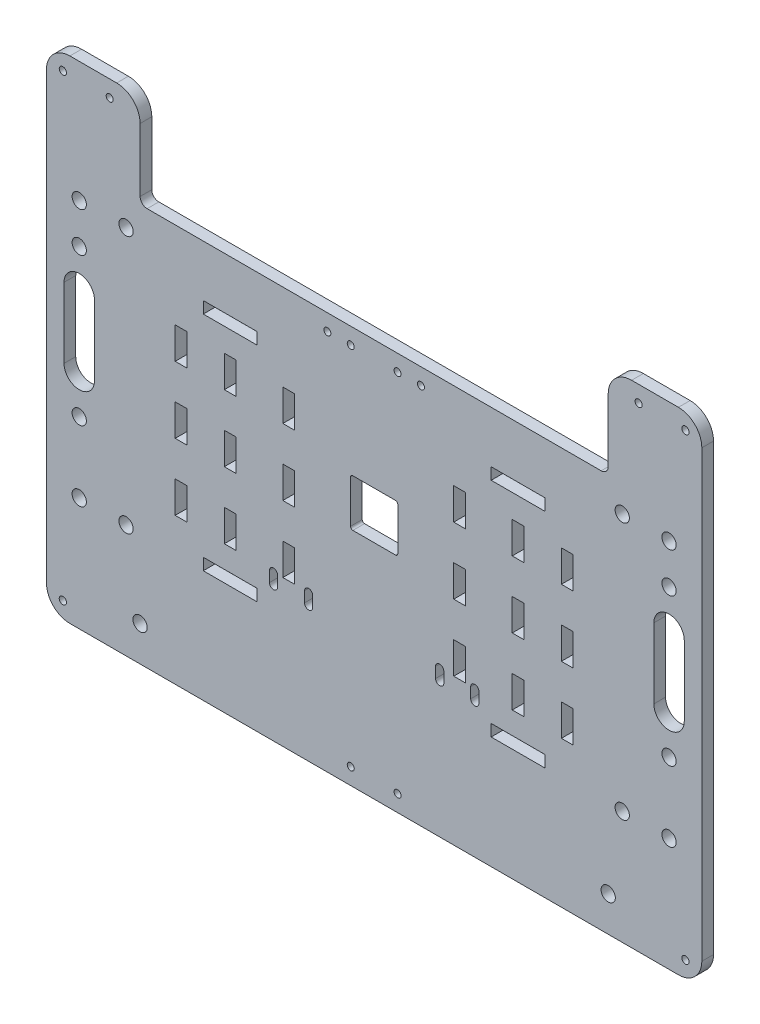
SolidWorks part; units mm, degrees
material "Acrylique (impact moyen-haut)"
ref_plane "Plan de face" through (0, 0, 0) normal (0, 0, 1) x (1, 0, 0)
ref_plane "Plan de dessus" through (0, 0, 0) normal (0, 1, 0) x (1, 0, 0)
ref_plane "Plan de droite" through (0, 0, 0) normal (1, 0, 0) x (0, 0, -1)
sketch "Esquisse1" plane through (0, 0, 0) normal (0, 0, 1) x (1, 0, 0)
  line L1 (130, -105) -> (-130, -105)
  line L2 (140, -95) -> (140, 105)
  line L3 (140, 105) -> (-140, 105)
  line L4 (-140, -95) -> (-140, 105)
  line L5 (140, -105) -> (-140, 105) construction
  line L6 (140, 105) -> (-140, -105) construction
  arc A0 (130, -105) -> (140, -95) centre (130, -95) ccw
  arc A1 (-130, -105) -> (-140, -95) centre (-130, -95) cw
  point P0 (0, 0)
  dimension "D3" = 10
  dimension "D1" = 210
  dimension "D2" = 280
extrude "Boss.-Extru.1" add sketch "Esquisse1" along normal blind 5
sketch "Esquisse2" plane through (0, 0, 5) normal (0, 0, 1) x (1, 0, 0)
  line L0 (-39.01, -0.5) -> (-39.01, -14)
  line L1 (-39.01, 28) -> (-34, 28)
  line L2 (-39.01, 28) -> (-39.01, 14.5)
  line L3 (-39.01, 14.5) -> (-34, 14.5)
  line L4 (-34, 28) -> (-34, 14.5)
  line L5 (-39.01, -0.5) -> (-34, -0.5)
  line L6 (-34, -0.5) -> (-34, -14)
  line L7 (-39.01, -14) -> (-34, -14)
  line L8 (-39.01, -29) -> (-39.01, -42.5)
  line L9 (-39.01, -29) -> (-34, -29)
  line L10 (-34, -29) -> (-34, -42.5)
  line L11 (-39.01, -42.5) -> (-34, -42.5)
  line L12 (-64.01, -0.5) -> (-64.01, -14)
  line L13 (-64.01, 28) -> (-59, 28)
  line L14 (-64.01, 28) -> (-64.01, 14.5)
  line L15 (-64.01, 14.5) -> (-59, 14.5)
  line L16 (-59, 28) -> (-59, 14.5)
  line L17 (-64.01, -0.5) -> (-59, -0.5)
  line L18 (-59, -0.5) -> (-59, -14)
  line L19 (-64.01, -14) -> (-59, -14)
  line L20 (-64.01, -29) -> (-64.01, -42.5)
  line L21 (-64.01, -29) -> (-59, -29)
  line L22 (-59, -29) -> (-59, -42.5)
  line L23 (-64.01, -42.5) -> (-59, -42.5)
  line L24 (-85.01, 28) -> (-85.01, 14.5)
  line L25 (-85.01, 28) -> (-80, 28)
  line L26 (-85.01, -0.5) -> (-85.01, -14)
  line L27 (-85.01, 14.5) -> (-80, 14.5)
  line L28 (-80, 28) -> (-80, 14.5)
  line L29 (-85.01, -0.5) -> (-80, -0.5)
  line L30 (-80, -0.5) -> (-80, -14)
  line L31 (-85.01, -14) -> (-80, -14)
  line L32 (-85.01, -29) -> (-85.01, -42.5)
  line L33 (-85.01, -29) -> (-80, -29)
  line L34 (-80, -29) -> (-80, -42.5)
  line L35 (-85.01, -42.5) -> (-80, -42.5)
  line L36 (85.01, 14.5) -> (80, 14.5)
  line L37 (50, -51.99) -> (50, -57)
  line L38 (73.01, -57) -> (50, -57)
  line L39 (73.01, -51.99) -> (73.01, -57)
  line L40 (73.01, -51.99) -> (50, -51.99)
  line L41 (50, 43) -> (50, 37.99)
  line L42 (73.01, 37.99) -> (50, 37.99)
  line L43 (73.01, 43) -> (73.01, 37.99)
  line L44 (73.01, 43) -> (50, 43)
  line L45 (85.01, -42.5) -> (80, -42.5)
  line L46 (80, -29) -> (80, -42.5)
  line L47 (85.01, -29) -> (80, -29)
  line L48 (85.01, -29) -> (85.01, -42.5)
  line L49 (85.01, -14) -> (80, -14)
  line L50 (80, -0.5) -> (80, -14)
  line L51 (85.01, -0.5) -> (80, -0.5)
  line L52 (80, 28) -> (80, 14.5)
  line L53 (85.01, 14.5) -> (80, 14.5)
  line L54 (85.01, -0.5) -> (85.01, -14)
  line L55 (85.01, 28) -> (80, 28)
  line L56 (85.01, 28) -> (85.01, 14.5)
  line L57 (64.01, -42.5) -> (59, -42.5)
  line L58 (59, -29) -> (59, -42.5)
  line L59 (64.01, -29) -> (59, -29)
  line L60 (64.01, -29) -> (64.01, -42.5)
  line L61 (64.01, -14) -> (59, -14)
  line L62 (59, -0.5) -> (59, -14)
  line L63 (64.01, -0.5) -> (59, -0.5)
  line L64 (59, 28) -> (59, 14.5)
  line L65 (64.01, 14.5) -> (59, 14.5)
  line L66 (64.01, 28) -> (64.01, 14.5)
  line L67 (64.01, 28) -> (59, 28)
  line L68 (64.01, -0.5) -> (64.01, -14)
  line L69 (39.01, -42.5) -> (34, -42.5)
  line L70 (34, -29) -> (34, -42.5)
  line L71 (39.01, -29) -> (34, -29)
  line L72 (39.01, -29) -> (39.01, -42.5)
  line L73 (39.01, -14) -> (34, -14)
  line L74 (0, 0) -> (0, 77.3847) construction
  line L75 (-73.01, 43) -> (-50, 43)
  line L76 (-73.01, 43) -> (-73.01, 37.99)
  line L77 (-73.01, 37.99) -> (-50, 37.99)
  line L78 (-50, 43) -> (-50, 37.99)
  line L79 (-73.01, -51.99) -> (-50, -51.99)
  line L80 (-73.01, -51.99) -> (-73.01, -57)
  line L81 (-73.01, -57) -> (-50, -57)
  line L82 (-50, -51.99) -> (-50, -57)
  line L83 (34, -0.5) -> (34, -14)
  line L84 (39.01, -0.5) -> (34, -0.5)
  line L85 (34, 28) -> (34, 14.5)
  line L86 (39.01, 14.5) -> (34, 14.5)
  line L87 (39.01, 28) -> (39.01, 14.5)
  line L88 (39.01, 28) -> (34, 28)
  line L89 (39.01, -0.5) -> (39.01, -14)
  line L90 (-140, 105) -> (-140, -95) construction
  line L91 (-130, -105) -> (130, -105) construction
  line L102 (-85.01, 14.5) -> (-80, 14.5)
  line L104 (-85.01, -0.5) -> (-80, -0.5)
  line L189 (-85.01, -0.5) -> (-85.01, -14) [skipped]
  line L190 (-85.01, 28) -> (-85.01, 14.5) [skipped]
  point P90 (81.49, 5)
  point P148 (-81.49, 5)
  dimension "D2" = 15
  dimension "D3" = 23.01
  dimension "D4" = 2
  dimension "D6" = 100
  dimension "D7" = 5.01
  dimension "D8" = 13.5
  dimension "D9" = 72
  dimension "D10" = 3
  dimension "D11" = 2
  dimension "D12" = 25
  dimension "D13" = 46
  dimension "D14" = 2
  dimension "D15" = 106
  dimension "D16" = 62.5
  dimension "D19" = 16
  dimension "D51" = 5.01
extrude "Enlèv. mat.-Extru.7" cut sketch "Esquisse2" against normal blind 10 contours L78 L75 L76 L77 | L16 L13 L14 L15 | L28 L25 L24 L27 | L26 L31 L30 L29 | L12 L19 L18 L17 | L20 L23 L22 L21 | L32 L35 L34 L33 | L82 L79 L80 L81 | L8 L11 L10 L9 | L4 L1 L2 L3 | L0 L7 L6 L5 | L87 L88 L85 L86 | L43 L44 L41 L42 | L66 L67 L64 L65 | L56 L55 L52 L36 | L48 L47 L46 L45 | L54 L51 L50 L49 | L68 L63 L62 L61 | L60 L59 L58 L57 | L39 L40 L37 L38 | L72 L71 L70 L69 | L89 L84 L83 L73
sketch "Esquisse3" plane through (0, 0, 5) normal (0, 0, 1) x (1, 0, 0)
  line L2 (-126, 5) -> (-60.3143, 5) construction
  line L3 (-126, 36.4988) -> (-126, -41.721) construction
  line L4 (-140, 105) -> (-140, -95) construction
  line L5 (0, 0) -> (0, 57.9816) construction
  line L6 (126, 36.4988) -> (126, -41.721) construction
  line L7 (126, 5) -> (60.3143, 5) construction
  line L10 (-73.01, 43) -> (-50, 43) construction
  circle A0 centre (-126, 36.4988) radius 3.05
  circle A1 centre (-126, -26.5012) radius 3.05
  circle A2 centre (-126, 53.4988) radius 3.05
  circle A3 centre (-126, -56.5012) radius 3.05
  circle A4 centre (-106, 53.4988) radius 3.05
  circle A5 centre (-106, -56.5012) radius 3.05
  circle A6 centre (106, -56.5012) radius 3.05
  circle A7 centre (106, 53.4988) radius 3.05
  circle A8 centre (126, -56.5012) radius 3.05
  circle A9 centre (126, 53.4988) radius 3.05
  circle A10 centre (126, -26.5012) radius 3.05
  circle A11 centre (126, 36.4988) radius 3.05
  point P1 (-126, 5)
  point P39 (113, 5)
  point P42 (-126, -26.5012)
  dimension "D2" = 6.1
  dimension "D6" = 63
  dimension "D10" = 31.4988
  dimension "D1" = 14
  dimension "D7" = 20
  dimension "D8" = 30
  dimension "D9" = 17
  dimension "D11" = 38
  dimension "D12" = 14
  dimension "D3" = 2
  dimension "D4" = 2
  dimension "D5" = 2
extrude "Enlèv. mat.-Extru.8" cut sketch "Esquisse3" against normal blind 5
sketch "Esquisse4" plane through (0, 0, 5) normal (0, 0, 1) x (1, 0, 0)
  line L0 (-126, 36.4988) -> (-126, -26.5012) construction
  line L1 (-126, -10.0012) -> (-126, 19.9988) construction
  line L2 (-132.5, -10.0012) -> (-132.5, 19.9988)
  line L3 (-119.5, -10.0012) -> (-119.5, 19.9988)
  line L4 (140, 105) -> (-140, 105) construction
  line L5 (0, 0) -> (0, 136.9763) construction
  line L6 (130, 105) -> (130.204, 105.2097)
  line L7 (140, 105) -> (130, 105)
  line L8 (140, 95) -> (140, 105)
  line L9 (100, 68) -> (100, 95)
  line L10 (-97, 65) -> (97, 65)
  line L11 (-100, 68) -> (-100, 95)
  line L14 (-140, 105) -> (-140, -95) construction
  line L15 (-140, 95) -> (-140, 105)
  line L16 (-140, 105) -> (-130, 105)
  line L17 (-130, 105) -> (-130.204, 105.2097)
  line L18 (-130, 105) -> (-110, 105)
  line L19 (110, 105) -> (130, 105)
  line L20 (-110, 105) -> (110, 105)
  line L21 (126, 36.4988) -> (126, -26.5012) construction
  line L22 (126, -10.0012) -> (126, 19.9988) construction
  line L23 (132.5, -10.0012) -> (132.5, 19.9988)
  line L24 (119.5, -10.0012) -> (119.5, 19.9988)
  arc A0 (-132.5, -10.0012) -> (-119.5, -10.0012) centre (-126, -10.0012) ccw
  arc A1 (-119.5, 19.9988) -> (-132.5, 19.9988) centre (-126, 19.9988) ccw
  arc A2 (-110, 105) -> (-100, 95) centre (-110, 95) cw
  arc A3 (-97, 65) -> (-100, 68) centre (-97, 68) cw
  arc A4 (-130, 105) -> (-140, 95) centre (-130, 95) ccw
  arc A5 (130, 105) -> (140, 95) centre (130, 95) cw
  arc A6 (97, 65) -> (100, 68) centre (97, 68) ccw
  arc A7 (110, 105) -> (100, 95) centre (110, 95) ccw
  arc A8 (132.5, -10.0012) -> (119.5, -10.0012) centre (126, -10.0012) cw
  arc A9 (119.5, 19.9988) -> (132.5, 19.9988) centre (126, 19.9988) cw
  point P6 (-126, 4.9988)
  point P20 (-110, 105)
  point P35 (-130, 95)
  point P47 (126, 4.9988)
  dimension "D6" = 10
  dimension "D7" = 3
  dimension "D8" = 10
  dimension "D1" = 13
  dimension "D2" = 30
  dimension "D3" = 40
  dimension "D4" = 194
  dimension "D5" = 220
extrude "Enlèv. mat.-Extru.12" cut sketch "Esquisse4" against normal blind 5 contours A7 L20 A2 L11 A3 L10 A6 L9 | A9 L24 A8 L23 | L3 A1 L2 A0 | A4 L15 L16 | A5 L8 L7 region at (-126, 4.9988, 5) region at (0, 85.1041, 5) region at (126, 4.9988, 5)
sketch "Esquisse5" plane through (0, 0, 5) normal (0, 0, 1) x (1, 0, 0)
  line L0 (-130, -105) -> (130, -105) construction
  line L1 (-140, 95) -> (-140, -95) construction
  line L2 (-97, 65) -> (97, 65) construction
  line L3 (-9.1, 10.1) -> (9.1, 10.1)
  line L4 (0, 0) -> (0, 69.856) construction
  line L5 (-10.1, 9.1) -> (-10.1, -9.1)
  line L6 (-110, 105) -> (-130, 105) construction
  line L7 (-9.1, -10.1) -> (9.1, -10.1)
  line L8 (10.1, 9.1) -> (10.1, -9.1)
  line L9 (-10.1, 10.1) -> (10.1, -10.1) construction
  line L10 (-10.1, -10.1) -> (10.1, 10.1) construction
  circle A0 centre (-100, -90) radius 3.05
  circle A1 centre (-133, -98) radius 1.55
  arc A2 (-10.1, -9.1) -> (-9.1, -10.1) centre (-9.1, -9.1) ccw
  circle A3 centre (-133, 98) radius 1.55
  circle A4 centre (133, -98) radius 1.55
  circle A5 centre (100, -90) radius 3.05
  circle A6 centre (133, 98) radius 1.55
  arc A7 (9.1, -10.1) -> (10.1, -9.1) centre (9.1, -9.1) ccw
  arc A8 (9.1, 10.1) -> (10.1, 9.1) centre (9.1, 9.1) cw
  arc A9 (-9.1, 10.1) -> (-10.1, 9.1) centre (-9.1, 9.1) ccw
  circle A10 centre (-113, 98) radius 1.5
  circle A11 centre (113, 98) radius 1.5
  circle A12 centre (-10, -98) radius 1.5
  circle A13 centre (10, -98) radius 1.5
  circle A14 centre (-20, 58) radius 1.5
  circle A15 centre (-10, 58) radius 1.5
  circle A16 centre (10, 58) radius 1.5
  circle A17 centre (20, 58) radius 1.5
  dimension "D1" = 6.1
  dimension "D4" = 3.1
  dimension "D7" = 1
  dimension "D8" = 3.1
  dimension "D12" = 3
  dimension "D14" = 3
  dimension "D17" = 3
  dimension "D18" = 3
  dimension "D2" = 15
  dimension "D3" = 40
  dimension "D5" = 7
  dimension "D6" = 7
  dimension "D9" = 7
  dimension "D10" = 7
  dimension "20.2" = 20.2
  dimension "D11" = 20.2
  dimension "D13" = 20
  dimension "D15" = 10
  dimension "D16" = 7
  dimension "D19" = 7
  dimension "D20" = 10
  dimension "D21" = 10
extrude "Enlèv. mat.-Extru.13" cut sketch "Esquisse5" against normal blind 5
sketch "Esquisse6" plane through (0, 0, 5) normal (0, 0, 1) x (1, 0, 0)
  line L0 (-43, -40.7207) -> (-43, -49.2793) construction
  line L1 (-43, -42.75) -> (-43, -47.25) construction
  line L2 (-41.25, -42.75) -> (-41.25, -47.25)
  line L3 (-44.75, -42.75) -> (-44.75, -47.25)
  line L4 (-73.01, -57) -> (-50, -57) construction
  line L5 (-34, -29) -> (-34, -42.5) construction
  line L6 (-28, -40.7207) -> (-28, -49.2793) construction
  line L7 (-28, -42.75) -> (-28, -47.25) construction
  line L8 (-26.25, -42.75) -> (-26.25, -47.25)
  line L9 (-29.75, -42.75) -> (-29.75, -47.25)
  line L10 (0, -63.5571) -> (0, 0) construction
  line L11 (28, -40.7207) -> (28, -49.2793) construction
  line L12 (43, -40.7207) -> (43, -49.2793) construction
  line L13 (28, -42.75) -> (28, -47.25) construction
  line L14 (26.25, -42.75) -> (26.25, -47.25)
  line L15 (29.75, -42.75) -> (29.75, -47.25)
  line L16 (43, -42.75) -> (43, -47.25) construction
  line L17 (41.25, -42.75) -> (41.25, -47.25)
  line L18 (44.75, -42.75) -> (44.75, -47.25)
  arc A0 (-41.25, -42.75) -> (-44.75, -42.75) centre (-43, -42.75) ccw
  arc A1 (-44.75, -47.25) -> (-41.25, -47.25) centre (-43, -47.25) ccw
  arc A2 (-26.25, -42.75) -> (-29.75, -42.75) centre (-28, -42.75) ccw
  arc A3 (-29.75, -47.25) -> (-26.25, -47.25) centre (-28, -47.25) ccw
  arc A4 (26.25, -42.75) -> (29.75, -42.75) centre (28, -42.75) cw
  arc A5 (29.75, -47.25) -> (26.25, -47.25) centre (28, -47.25) cw
  arc A6 (41.25, -42.75) -> (44.75, -42.75) centre (43, -42.75) cw
  arc A7 (44.75, -47.25) -> (41.25, -47.25) centre (43, -47.25) cw
  point P4 (-43, -45)
  point P18 (-28, -45)
  point P31 (28, -45)
  point P38 (43, -45)
  dimension "D1" = 3.5
  dimension "D2" = 4.5
  dimension "D3" = 12
  dimension "D4" = 9
extrude "Enlèv. mat.-Extru.14" cut sketch "Esquisse6" against normal blind 5
